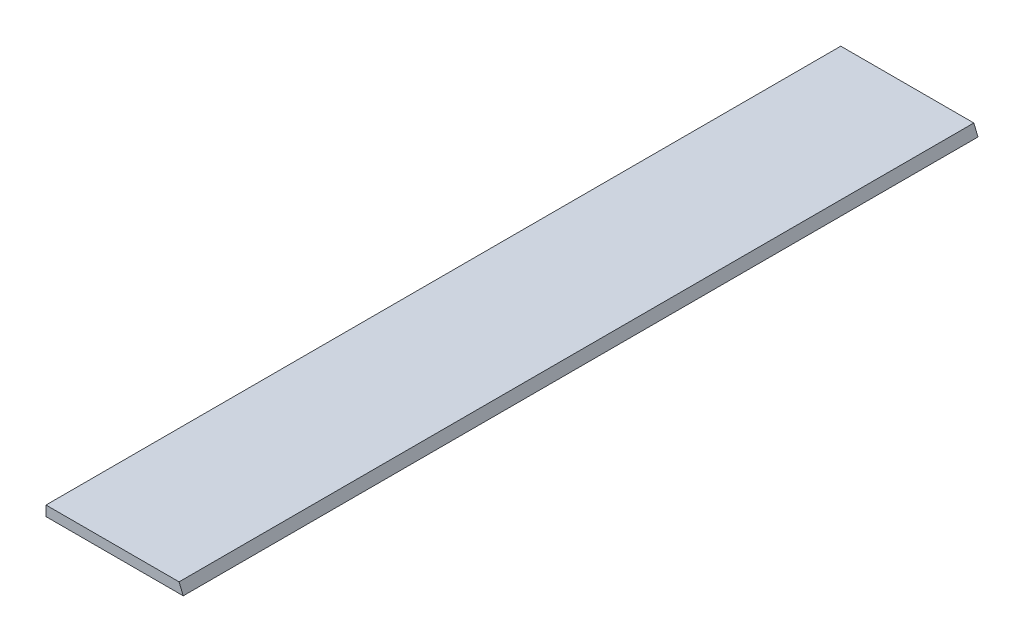
SolidWorks part; units mm, degrees
ref_plane "Front Plane" through (0, 0, 0) normal (0, 0, 1) x (1, 0, 0)
ref_plane "Top Plane" through (0, 0, 0) normal (0, 1, 0) x (1, 0, 0)
ref_plane "Right Plane" through (0, 0, 0) normal (1, 0, 0) x (0, 0, -1)
sketch "Sketch1" plane through (0, 0, 0) normal (0, 0, 1) x (1, 0, 0)
  line L0 (0, 0) -> (0, 6.35)
  line L1 (0, 6.35) -> (83.9837, 6.35)
  line L2 (83.9837, 6.35) -> (86.614, 0)
  line L3 (86.614, 0) -> (0, 0)
  dimension "D1" = 6.35
  dimension "D2" = 67.5
  dimension "D3" = 86.614
extrude "Boss-Extrude1" add sketch "Sketch1" along normal blind 501.65
